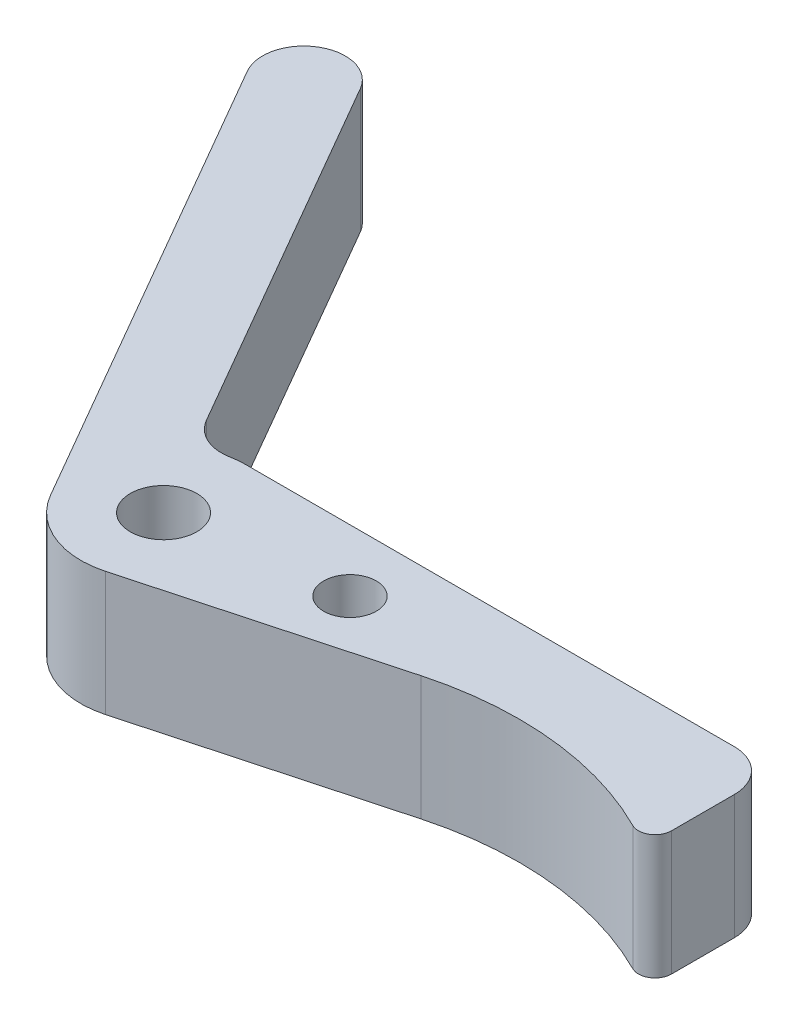
SolidWorks part; units mm, degrees
material "6061-T6 (SS)"
ref_plane "Front" through (0, 0, 0) normal (0, 0, 1) x (1, 0, 0)
ref_plane "Top" through (0, 0, 0) normal (0, 1, 0) x (1, 0, 0)
ref_plane "Right" through (0, 0, 0) normal (1, 0, 0) x (0, 0, -1)
sketch "Sketch1" plane through (0, 0, 0) normal (0, 1, 0) x (1, 0, 0)
  line L0 (0, 6.35) -> (40.64, 6.35)
  line L1 (40.64, 6.35) -> (40.64, -3.81)
  line L2 (1.664, -6.1281) -> (20.714, -0.9554)
  line L3 (-3.175, 5.4993) -> (-22.225, 38.4948)
  line L4 (-22.225, 38.4948) -> (-27.7243, 35.3198)
  line L5 (-27.7243, 35.3198) -> (-5.4993, -3.175)
  circle A0 centre (0, 0) radius 2.5527
  circle A1 centre (0, 0) radius 6.35
  arc A2 (20.714, -0.9554) -> (40.64, -3.81) centre (27.3699, -25.4679) cw
  point P12 (-53.266, 31.468)
  point P13 (-31.8966, 22.023)
  point P16 (-31.197, 31.6631)
  point P17 (-31.2265, 31.634)
  point P18 (-24.9375, 37.3396)
  dimension "D1" = 5.1054
  dimension "D2" = 12.7
  dimension "D5" = 19.05
  dimension "D7" = 38.1
  dimension "D6" = 25.4
  dimension "D3" = 40.64
  dimension "D4" = 10.16
  dimension "D8" = 6.35
  dimension "D9" = 3.175
extrude "Boss-Extrude1" add sketch "Sketch1" along normal blind 9.525 contours A1 A0 | L2 A2 L1 L0 A1 | A1 L3 L4 L5 region at (21.7984, 0, -2.1451) region at (4.3631, 0, -4.3631) region at (-15.1488, 0, -19.7671)
fillet "Fillet1" radius 3.175 4 edges at (40.64, 4.7625, -6.35) (-3.175, 4.7625, -5.4993) (-27.7243, 4.7625, -35.3198) (-22.225, 4.7625, -38.4948)
fillet "Fillet2" radius 1.27 1 edges at (40.64, 4.7625, 3.81)
sketch "Sketch5" plane through (0, 9.525, 0) normal (0, 1, 0) x (1, 0, 0)
  line L0 (12.7, -3.1315) -> (12.7, 6.35) construction
  line L1 (0, 6.35) -> (37.465, 6.35) construction
  line L3 (1.664, -6.1281) -> (20.714, -0.9554) construction
  point P0 (12.7, 1.6093)
  point P36 (12.7, 1.6093)
  point P39 (14.1608, -2.7348)
  point P42 (13.7163, 1.7472)
  point P43 (13.6161, 1.7336)
  dimension "D1" = 12.7
hole_wizard "#10-32 Tapped Hole1" positions "Sketch5" profile "Sketch3" tap size "#10-32" standard "ANSI Inch" end condition through all
sketch "Sketch3" plane through (12.7, 9.525, -1.6093) normal (1, 0, 0) x (0, 0, 1)
  line L0 (0, 0) -> (0, 9.525)
  line L1 (0, 9.525) -> (2.0193, 9.525)
  line L2 (2.0193, 9.525) -> (2.0193, 0)
  line L5 (2.0193, 0) -> (0, 0)
  line L11 (0, -6.35) -> (0, 107.95) construction
  dimension "Thru Tap Drill Dia." = 4.0386
  dimension "Thru Tap Drill Depth" = 9.525
cosmetic thread "Hole Thread1" parameters "D2"=4.826
cosmetic thread "Hole Thread2" parameters "D2"=4.826
